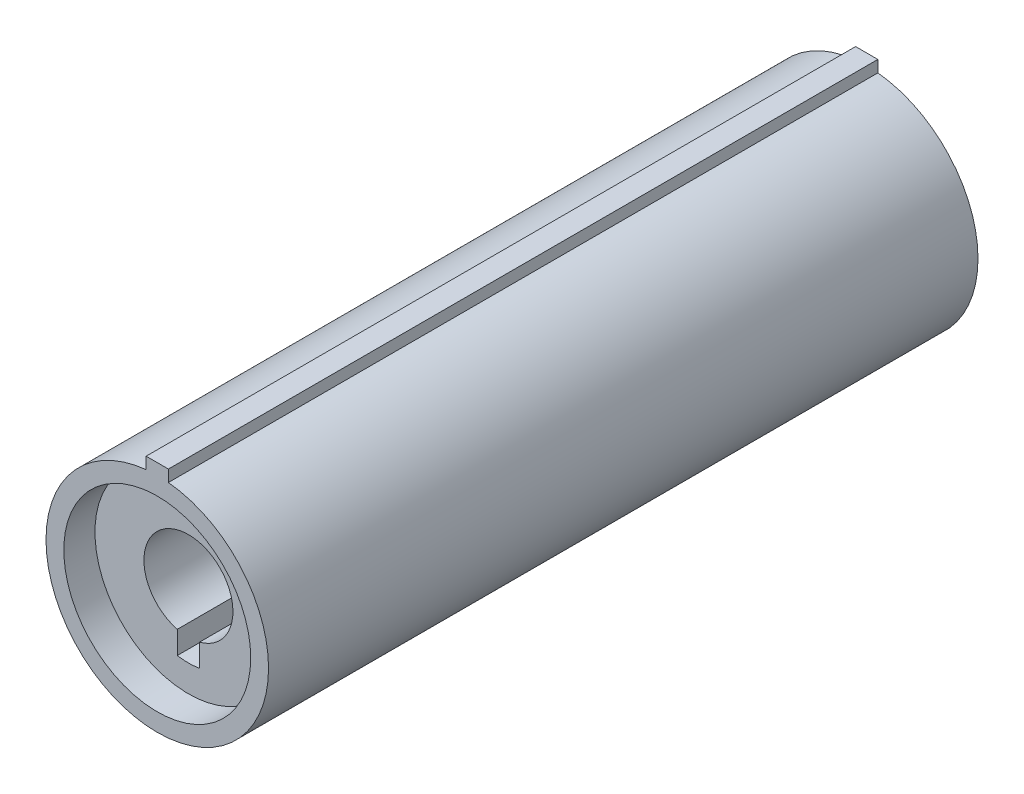
SolidWorks part; units mm, degrees
ref_plane "Front Plane" through (0, 0, 0) normal (0, 0, 1) x (1, 0, 0)
ref_plane "Top Plane" through (0, 0, 0) normal (0, 1, 0) x (1, 0, 0)
ref_plane "Right Plane" through (0, 0, 0) normal (1, 0, 0) x (0, 0, -1)
sketch "Sketch1" plane through (0, 0, 0) normal (0, 0, 1) x (1, 0, 0)
  line L3 (-2.5, 24.8747) -> (-2.5, 27.5)
  line L4 (-2.5, 27.5) -> (2.5, 27.5)
  line L5 (2.5, 27.5) -> (2.5, 24.8747)
  line L8 (-2.5, -9.6825) -> (-2.5, -25)
  line L9 (-2.5, -25) -> (2.5, -25)
  line L10 (2.5, -9.6825) -> (2.5, -25)
  arc A0 (-2.5, 24.8747) -> (2.5, 24.8747) centre (0, 0) ccw
  arc A1 (2.5, -9.6825) -> (-2.5, -9.6825) centre (0, 0) ccw
  point P12 (0, 27.5)
  point P13 (0, -25)
  dimension "D1" = 20
  dimension "D2" = 50
  dimension "D3" = 5
  dimension "D5" = 27.5
extrude "Boss-Extrude1" add sketch "Sketch1" along normal blind 152.4 contours A1 L10 A0 L5 L4 L3 L8 region at (-1.7759, 26.1873, 0)
sketch "Sketch3" plane through (0, 0, 152.4) normal (0, 0, 1) x (1, 0, 0)
  line L6 (-2.5, 27.5) -> (2.5, 27.5)
  line L8 (-2.5, 27.5) -> (-2.5, 24.8747)
  line L10 (2.5, 27.5) -> (2.5, 24.8747)
  circle A0 centre (0, 0) radius 21
  arc A1 (-2.5, -24.8747) -> (2.5, 24.8747) centre (0, 0) ccw
  arc A3 (-2.5, 24.8747) -> (-2.5, -24.8747) centre (0, 0) ccw
  arc A4 (-2.5, 24.8747) -> (-2.5, -24.8747) centre (0, 0) ccw construction
  dimension "D1" = 42
extrude "Boss-Extrude2" add sketch "Sketch3" along normal blind 7
sketch "Sketch4" plane through (0, 0, 152.4) normal (0, 0, 1) x (1, 0, 0)
  line L0 (2.5, -9.6825) -> (2.5, -20.8507) construction
  line L2 (-2.5, -14.7902) -> (-2.5, -24.8747)
  line L3 (2.5, -24.8747) -> (2.5, -14.7902)
  line L4 (-2.5, -9.6825) -> (-2.5, -20.8507) construction
  arc A0 (-2.5, -14.7902) -> (2.5, -14.7902) centre (0, 0) ccw
  arc A1 (-2.5, -9.6825) -> (2.5, -9.6825) centre (0, 0) ccw construction
  arc A2 (-2.5, -24.8747) -> (2.5, -24.8747) centre (0, 0) ccw
  arc A3 (-2.5, 24.8747) -> (2.5, 24.8747) centre (0, 0) ccw construction
  point P8 (0, -10)
  point P12 (0, -15)
  dimension "D1" = 5
extrude "Boss-Extrude3" add sketch "Sketch4" against normal up to surface (152.4 mm away) up to face at (0, 6.9147, 0)
